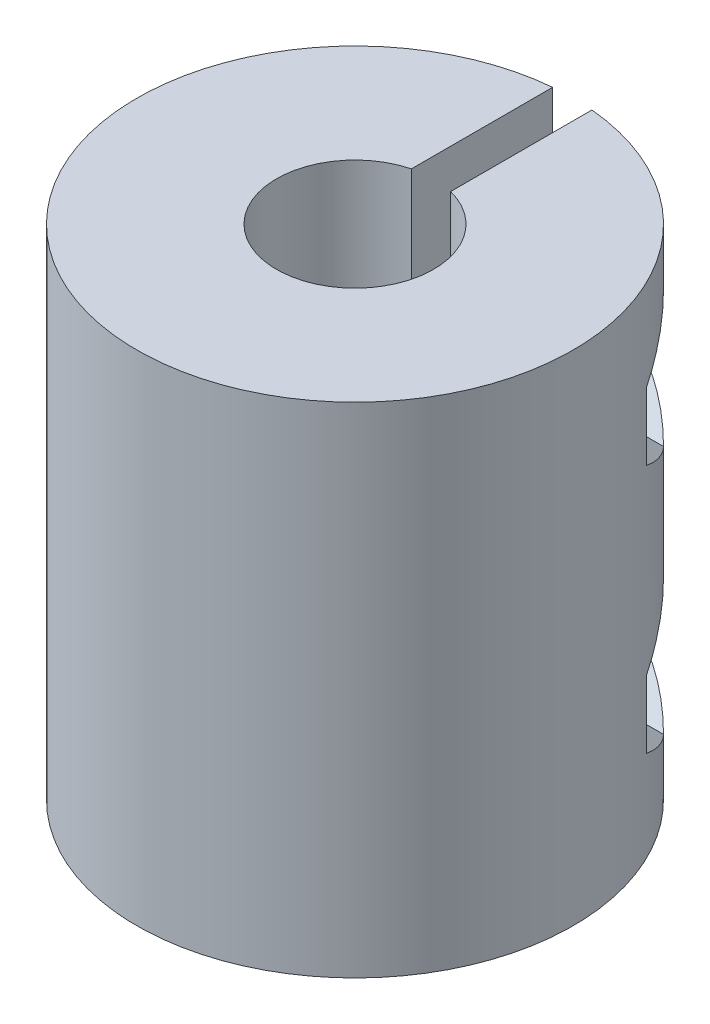
SolidWorks part; units mm, degrees
ref_plane "Front Plane" through (0, 0, 0) normal (0, 0, 1) x (1, 0, 0)
ref_plane "Top Plane" through (0, 0, 0) normal (0, 1, 0) x (1, 0, 0)
ref_plane "Right Plane" through (0, 0, 0) normal (1, 0, 0) x (0, 0, -1)
sketch "Sketch1" plane through (0, 0, 0) normal (0, 1, 0) x (1, 0, 0)
  circle A0 centre (0, 0) radius 11.1125
  dimension "D1" = 22.225
extrude "Boss-Extrude1" add sketch "Sketch1" along normal mid plane 25.4
sketch "Sketch2" plane through (0, 12.7, 0) normal (0, 1, 0) x (1, 0, 0)
  circle A0 centre (0, 0) radius 4
  dimension "D1" = 8
extrude "Cut-Extrude1" cut sketch "Sketch2" against normal up to surface (12.7 mm away) up to plane "Top Plane"
sketch "Sketch3" plane through (0, -12.7, 0) normal (0, -1, 0) x (1, 0, 0)
  circle A0 centre (0, 0) radius 4.7625
  dimension "D1" = 9.525
extrude "Cut-Extrude2" cut sketch "Sketch3" against normal up to surface (12.7 mm away) up to plane "Top Plane"
sketch "Sketch4" plane through (0, 12.7, 0) normal (0, 1, 0) x (1, 0, 0)
  line L0 (-1, 3.873) -> (-1, 11.0674)
  line L1 (1, 11.0674) -> (1, 3.873)
  circle A0 centre (0, 0) radius 4 construction
  circle A1 centre (0, 0) radius 11.1125
  arc A2 (1, 11.0674) -> (-1, 11.0674) centre (0, 0) ccw
  arc A3 (1, 3.873) -> (-1, 3.873) centre (0, 0) ccw
  point P9 (0, 0)
  dimension "D2" = 2
  dimension "D1" = 0
extrude "Cut-Extrude3" cut sketch "Sketch4" against normal up to next
ref_plane "Plane1" through (7, 0, 0) normal (-1, 0, 0) x (0, 0, 1)
sketch "Sketch5" plane through (7, 0, 0) normal (1, 0, 0) x (0, 0, -1)
  line L0 (7.8619, -6.35) -> (7.8619, 6.35) construction
  line L1 (7.8619, 2.8859) -> (10.8619, 4.6179)
  line L2 (10.8619, 4.6179) -> (10.8619, 8.0821)
  line L3 (10.8619, 8.0821) -> (7.8619, 9.8141)
  line L4 (7.8619, 9.8141) -> (4.8619, 8.0821)
  line L5 (4.8619, 8.0821) -> (4.8619, 4.6179)
  line L6 (4.8619, 4.6179) -> (7.8619, 2.8859)
  line L7 (7.8619, -9.8141) -> (10.8619, -8.0821)
  line L8 (10.8619, -8.0821) -> (10.8619, -4.6179)
  line L9 (10.8619, -4.6179) -> (7.8619, -2.8859)
  line L10 (7.8619, -2.8859) -> (4.8619, -4.6179)
  line L11 (4.8619, -4.6179) -> (4.8619, -8.0821)
  line L12 (4.8619, -8.0821) -> (7.8619, -9.8141)
  line L13 (11.0674, -12.7) -> (4.6563, -12.7) construction
  circle A0 centre (7.8619, 6.35) radius 3 construction
  circle A1 centre (7.8619, -6.35) radius 3 construction
  point P9 (7.8619, 0)
  point P17 (7.6642, 5.3253)
  point P21 (7.8619, -12.7)
  dimension "D1" = 6
  dimension "D2" = 6.35
extrude "Cut-Extrude4" cut sketch "Sketch5" against normal blind 4 and the other way up to next
hole_wizard "M3 Clearance Hole1" positions "Sketch6" profile "Sketch7" hole size "M3" standard "ANSI Metric" end condition through all
sketch "Sketch6" plane through (3, 0, 0) normal (1, 0, 0) x (0, 0, -1)
  point P0 (7.8619, 6.35)
  point P3 (7.8619, -6.35)
sketch "Sketch7" plane through (3, 6.35, -7.8619) normal (0, 1, 0) x (0, 0, -1)
  line L0 (0, 0) -> (0, 14.1125)
  line L1 (0, 14.1125) -> (1.7, 14.1125)
  line L2 (1.7, 14.1125) -> (1.7, 0)
  line L5 (1.7, 0) -> (0, 0)
  line L11 (0, -6.35) -> (0, 107.95) construction
  dimension "Thru Hole Dia." = 3.4
  dimension "Thru Hole Depth" = 14.1125
ref_plane "Plane2" through (-3, 0, 0) normal (1, 0, 0) x (0, 0, -1)
sketch "Sketch9" plane through (-3, 0, 0) normal (1, 0, 0) x (0, 0, -1)
  circle A0 centre (7.8619, 6.35) radius 3.5
  circle A1 centre (7.8619, -6.35) radius 3.5
  dimension "D1" = 7
extrude "Cut-Extrude5" cut sketch "Sketch9" against normal up to next
